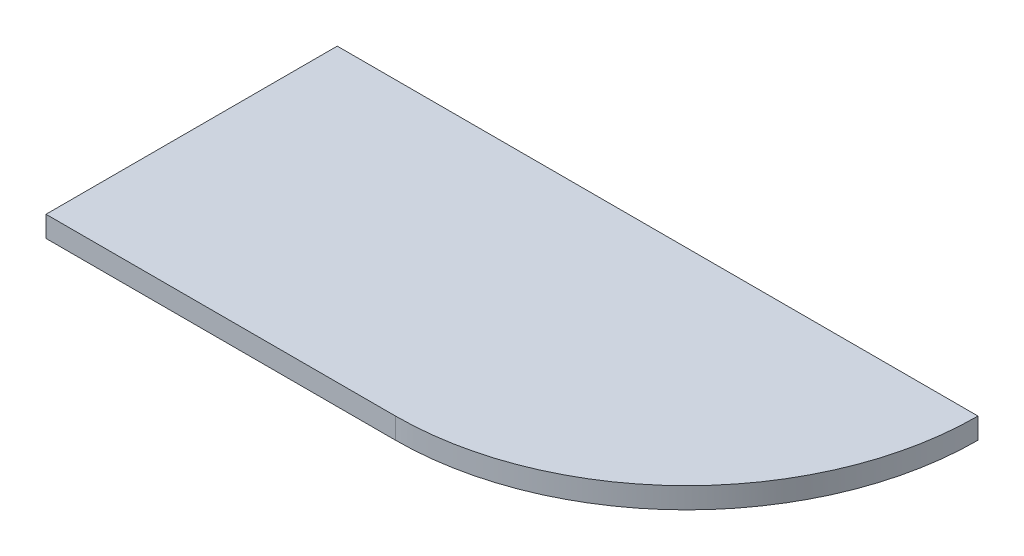
SolidWorks part; units mm, degrees
ref_plane "Front Plane" through (0, 0, 0) normal (0, 0, 1) x (1, 0, 0)
ref_plane "Top Plane" through (0, 0, 0) normal (0, 1, 0) x (1, 0, 0)
ref_plane "Right Plane" through (0, 0, 0) normal (1, 0, 0) x (0, 0, -1)
sketch "Sketch1" plane through (0, 0, 0) normal (0, 1, 0) x (1, 0, 0)
  line L1 (25.001, -125) -> (-275, -125)
  line L2 (275, 124.999) -> (275, 125)
  line L3 (275, 125) -> (-275, 125)
  line L4 (-275, -125) -> (-275, 125)
  line L5 (275, -125) -> (-275, 125) construction
  line L6 (275, 125) -> (-275, -125) construction
  arc A0 (275, 124.999) -> (25.001, -125) centre (25.001, 124.999) cw
  point P0 (0, 0)
  dimension "D3" = 249.999
  dimension "D1" = 250
  dimension "D2" = 550
extrude "Boss-Extrude1" add sketch "Sketch1" along normal blind 18
equation "\"H_DSP\"=18"
equation "\"D1@Boss-Extrude1\"=\"H_DSP\""
